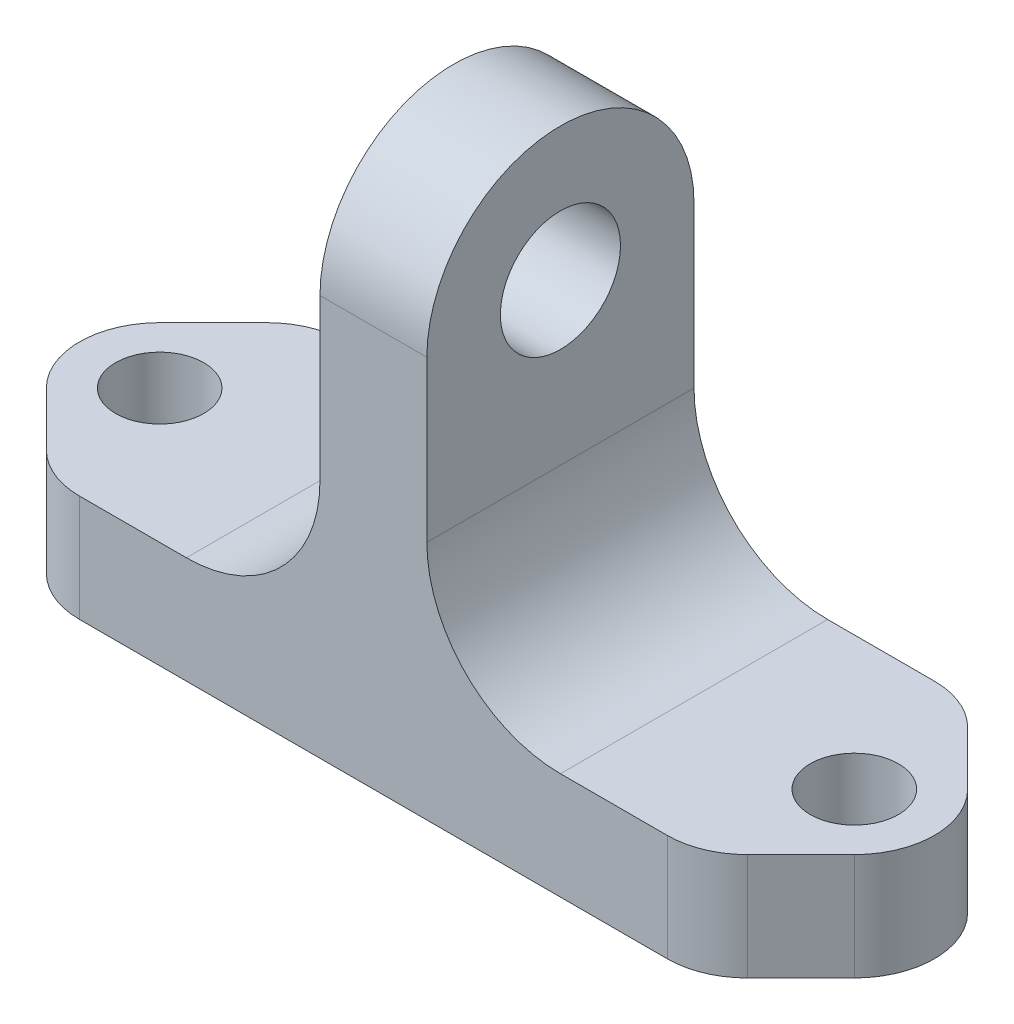
SolidWorks part; units mm, degrees
ref_plane "Front Plane" through (0, 0, 0) normal (0, 0, 1) x (1, 0, 0)
ref_plane "Top Plane" through (0, 0, 0) normal (0, 1, 0) x (1, 0, 0)
ref_plane "Right Plane" through (0, 0, 0) normal (1, 0, 0) x (0, 0, -1)
sketch "Sketch1" plane through (0, 0, 0) normal (0, 0, 1) x (1, 0, 0)
  line L0 (-16, 0) -> (16, 0)
  line L1 (16, 0) -> (16, 4)
  line L2 (16, 4) -> (2, 4)
  line L3 (2, 4) -> (2, 20)
  line L4 (2, 20) -> (-2, 20)
  line L5 (-2, 20) -> (-2, 4)
  line L6 (-2, 4) -> (-16, 4)
  line L7 (-16, 4) -> (-16, 0)
  line L8 (-13, 12.0198) -> (-13, -10.4145) construction
  point P11 (-13, 12.0198)
  point P12 (0, 0)
  point P13 (0, 20)
  dimension "D1" = 13
  dimension "D2" = 4
  dimension "D3" = 4
  dimension "D4" = 3
  dimension "D5" = 20
extrude "Boss-Extrude1" add sketch "Sketch1" along normal mid plane 10 contours L5 L6 L7 L0 L1 L2 L3 L4
hole_wizard "Ø3.3 (3.3) Diameter Hole1" positions "Sketch2" profile "Sketch3" hole size "Ø3.3" standard "ANSI Metric" end condition through all
sketch "Sketch2" plane through (0, 4, 0) normal (0, 1, 0) x (1, 0, 0)
  line L0 (-13, 0) -> (13, 0) construction
  point P0 (-13, 0)
  point P2 (13, 0)
  dimension "D1" = 26
sketch "Sketch3" plane through (-13, 4, 0) normal (1, 0, 0) x (0, 0, 1)
  line L0 (0, 0) -> (0, 4)
  line L1 (0, 4) -> (1.65, 4)
  line L2 (1.65, 4) -> (1.65, 0)
  line L5 (1.65, 0) -> (0, 0)
  line L11 (0, -6.35) -> (0, 107.95) construction
  dimension "Thru Hole Dia." = 3.3
  dimension "Thru Hole Depth" = 4
fillet "Fillet1" 2 edges at (0, 20, 5) (0, 20, -5) type full round first side face at (0, 7, 5) second side face at (0, 7, -5) middle face at (0, 20, 0)
fillet "Fillet2" radius 5 2 edges at (-2, 4, 0) (2, 4, 0)
hole_wizard "#16 (0.177) Diameter Hole1" positions "Sketch4" profile "Sketch5" hole size "#16" standard "ANSI Inch" end condition up to next
sketch "Sketch4" plane through (2, 0, 0) normal (1, 0, 0) x (0, 0, -1)
  point P0 (0, 15)
sketch "Sketch5" plane through (2, 15, 0) normal (0, 1, 0) x (0, 0, -1)
  line L0 (0, 0) -> (0, 4)
  line L1 (0, 4) -> (2.2479, 4)
  line L2 (2.2479, 4) -> (2.2479, 0)
  line L5 (2.2479, 0) -> (0, 0)
  line L11 (0, -6.35) -> (0, 107.95) construction
  dimension "Thru Hole Dia." = 4.4958
  dimension "Thru Hole Depth" = 4
sketch "Sketch6" plane through (0, 0, 0) normal (0, 1, 0) x (1, 0, 0)
  line L0 (-15.1213, 2.1213) -> (-13.1213, 4.1213)
  line L1 (-15.1213, -2.1213) -> (-13.1213, -4.1213)
  line L2 (-11, 5) -> (-16, 5)
  line L3 (-7, 5) -> (-16, 5) construction
  line L4 (-16, 5) -> (-16, -5)
  line L5 (-16, -5) -> (-11, -5)
  line L6 (-7, -5) -> (-16, -5) construction
  arc A0 (-15.1213, 2.1213) -> (-15.1213, -2.1213) centre (-13, 0) ccw
  arc A1 (-13.1213, -4.1213) -> (-11, -5) centre (-11, -2) ccw
  arc A2 (-11, 5) -> (-13.1213, 4.1213) centre (-11, 2) ccw
  point P4 (0, 0)
  point P8 (-10.9114, -5)
  point P15 (-12.0575, 5)
  point P20 (-11.3447, 5)
  point P22 (-11.2329, 5)
extrude "Cut-Extrude1" cut sketch "Sketch6" along normal up to next contours A0 L4 L5 L1 | A0 L0 L2 L4 region at (-14.7083, 0, -3.7083) region at (-14.7083, 0, 3.7083)
mirror "Mirror1" about plane through (0, 0, 0) normal (1, 0, 0) of "Cut-Extrude1"
equation "\"D3@Sketch1\"=\"D2@Sketch1\""
